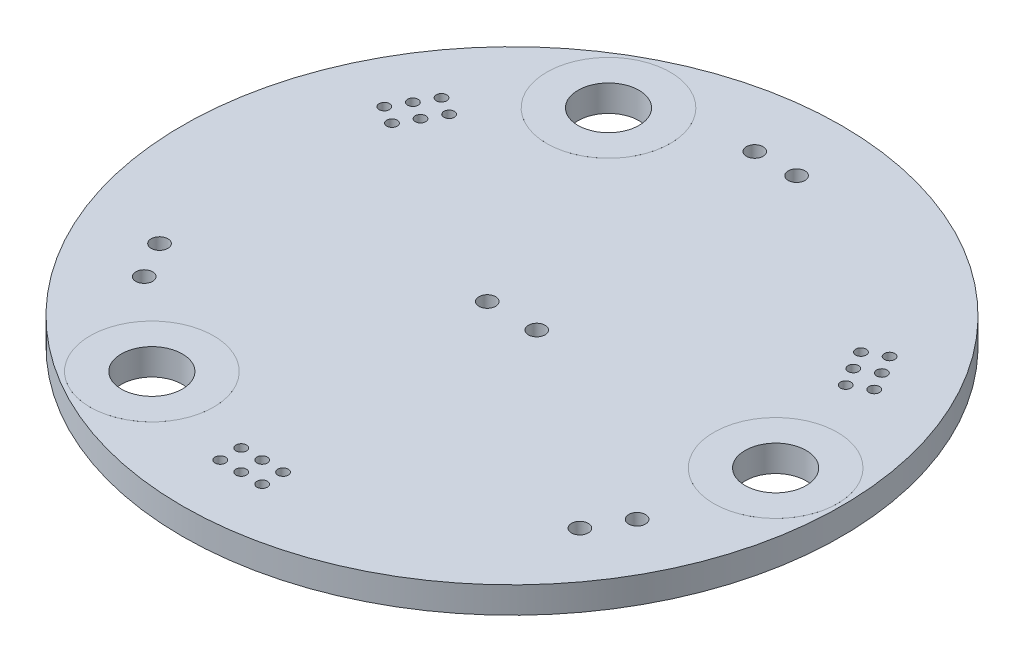
SolidWorks part; units mm, degrees
ref_plane "Front Plane" through (0, 0, 0) normal (0, 0, 1) x (1, 0, 0)
ref_plane "Top Plane" through (0, 0, 0) normal (0, 1, 0) x (1, 0, 0)
ref_plane "Right Plane" through (0, 0, 0) normal (1, 0, 0) x (0, 0, -1)
sketch "Sketch1" plane through (0, 0, 0) normal (0, 1, 0) x (1, 0, 0)
  circle A0 centre (0, 0) radius 20
  dimension "D1" = 40
extrude "Boss-Extrude1" add sketch "Sketch1" along normal blind 1.6
sketch "Sketch2" plane through (0, 1.6, 0) normal (0, 1, 0) x (1, 0, 0)
  line L0 (0, 0) -> (16, 0) construction
  circle A0 centre (16, 0) radius 1.85
  circle A2 centre (-8, -13.8564) radius 1.85
  circle A3 centre (-8, 13.8564) radius 1.85
  point P14 (0, 0)
  dimension "D1" = 16
  dimension "D2" = 3.7
  dimension "D3" = 3
extrude "Cut-Extrude1" cut sketch "Sketch2" against normal through all
ref_axis "Axis1" through (0, 1.6, 0) along (0, -1, 0)
ref_plane "Plane1" through (0, 0, 0) normal (0.866, 0, 0.5) x (0, -1, 0)
sketch "Sketch3" plane through (0, 1.6, 0) normal (0, 1, 0) x (1, 0, 0)
  circle A24 centre (-1.5, 0) radius 0.508
  circle A25 centre (-1.5, 0) radius 0.25 construction
  circle A26 centre (1.5, 0) radius 0.508
  circle A27 centre (1.5, 0) radius 0.25 construction
  circle A43 centre (1.27, 16) radius 0.508
  circle A44 centre (1.27, 16) radius 0.9 construction
  circle A45 centre (-1.27, 16) radius 0.508
  circle A46 centre (-1.27, 16) radius 0.9 construction
  circle A47 centre (13.2214, -9.0999) radius 0.508
  circle A48 centre (14.4914, -6.9001) radius 0.508
  circle A49 centre (-14.4914, -6.9001) radius 0.508
  circle A50 centre (-13.2214, -9.0999) radius 0.508
  circle A51 centre (1.27, -16.4332) radius 0.3175
  circle A52 centre (1.27, -15.1632) radius 0.3175
  circle A53 centre (0, -15.1632) radius 0.3175
  circle A54 centre (-1.27, -15.1632) radius 0.3175
  circle A55 centre (0, -16.4332) radius 0.3175
  circle A56 centre (-1.27, -16.4332) radius 0.3175
  circle A57 centre (-14.8666, 7.1167) radius 0.3175
  circle A58 centre (-13.7667, 6.4817) radius 0.3175
  circle A59 centre (-13.1317, 7.5816) radius 0.3175
  circle A60 centre (-12.4967, 8.6815) radius 0.3175
  circle A61 centre (-14.2316, 8.2166) radius 0.3175
  circle A62 centre (-13.5966, 9.3165) radius 0.3175
  circle A63 centre (13.5966, 9.3165) radius 0.3175
  circle A64 centre (12.4967, 8.6815) radius 0.3175
  circle A65 centre (13.1317, 7.5816) radius 0.3175
  circle A66 centre (13.7667, 6.4817) radius 0.3175
  circle A67 centre (14.2316, 8.2166) radius 0.3175
  circle A68 centre (14.8666, 7.1167) radius 0.3175
  point P4 (11.5546, 12.3931)
  point P6 (-16.51, 3.81)
  point P54 (0, 0)
  point P64 (0, 0)
  point P82 (0, 0)
  dimension "D1" = 0.635
  dimension "D2" = 2
  dimension "D3" = 3
  dimension "D4" = 3
extrude "Cut-Extrude2" cut sketch "Sketch3" against normal through all
sketch "Sketch5" plane through (0, 1.6, 0) normal (0, 1, 0) x (1, 0, 0)
  circle A0 centre (-8, -13.8564) radius 3.75
  circle A1 centre (-8, 13.8564) radius 3.75
  circle A2 centre (16, 0) radius 3.75
  point P9 (0, 0)
  circle M28 centre (16, 0) radius 1.85
  circle M29 centre (-8, -13.8564) radius 1.85
  circle M30 centre (-8, 13.8564) radius 1.85
  dimension "D1" = 7.5
  dimension "D2" = 3
extrude "Boss-Extrude2" add sketch "Sketch5" along normal blind 0.001 contours A0 M29 | A1 M30 | A2 M28 region at (-11.6439, 1.6, 13.8564) region at (-11.6439, 1.6, -13.8564) region at (12.3561, 1.6, 0)
ref_plane "Plane2" through (0, 0.8, 0) normal (0, 1, 0) x (1, 0, 0)
mirror "Mirror1" about plane through (0, 0.8, 0) normal (0, 1, 0) of "Boss-Extrude2"
sketch "Sketch6" plane through (0, 0, 0) normal (0, 1, 0) x (1, 0, 0)
  line L1 (-9.563, 4.0609) -> (9.563, 4.0609) construction
  text T0 "Conn PCB" font "Century Gothic" height 2.5
  point P2 (0, 4.0609)
extrude "Boss-Extrude3" add sketch "Sketch6" against normal blind 0.001
sketch "Sketch4" plane through (0, 1.6, 0) normal (0, 1, 0) x (1, 0, 0)
  line L1 (-7.62, -2.71) -> (-7.62, -3.01) construction
  line L2 (-7.62, -3.01) -> (-5.08, -3.01) construction
  line L3 (-5.08, -3.01) -> (-5.08, -2.71) construction
  line L4 (-5.08, -2.71) -> (-7.62, -2.71) construction
  line L5 (7.62, -7.79) -> (7.62, -7.49) construction
  line L6 (7.62, -7.49) -> (5.08, -7.49) construction
  line L7 (5.08, -7.49) -> (5.08, -7.79) construction
  line L8 (5.08, -7.79) -> (7.62, -7.79) construction
  line L9 (-7.62, -2.71) -> (-7.62, -3.01)
  line L10 (-7.62, -3.01) -> (-5.08, -3.01)
  line L11 (-5.08, -3.01) -> (-5.08, -2.71)
  line L12 (-5.08, -2.71) -> (-7.62, -2.71)
  line L13 (7.62, -7.79) -> (7.62, -7.49)
  line L14 (7.62, -7.49) -> (5.08, -7.49)
  line L15 (5.08, -7.49) -> (5.08, -7.79)
  line L16 (5.08, -7.79) -> (7.62, -7.79)
  line L17 (7.62, -7.79) -> (-7.62, -2.71) construction
  point P0 (-8, -13.8564)
  point P1 (-13.2214, -9.0999)
  point P3 (1.27, -15.1632)
  point P5 (-8, 13.8564)
  point P7 (16, 0)
  point P9 (-14.8666, 7.1167)
  point P12 (13.5966, 9.3165)
  point P14 (1.27, -16.4332)
  point P16 (14.4914, -6.9001)
  point P18 (0, -5.25)
  point P19 (-1.27, 16)
  dimension "D1" = 8
  dimension "D2" = 13.8564
  dimension "D3" = 13.8564
  dimension "D4" = 16
  dimension "D5" = 16.4332
  dimension "D6" = 14.8666
  dimension "D7" = 7.1167
  dimension "D8" = 13.5966
  dimension "D9" = 9.3165
  dimension "D10" = 13.2214
  dimension "D11" = 9.0999
  dimension "D12" = 16
  dimension "D13" = 1.27
  dimension "D14" = 6.9001
  dimension "D15" = 14.4914
  dimension "D16" = 5.25
